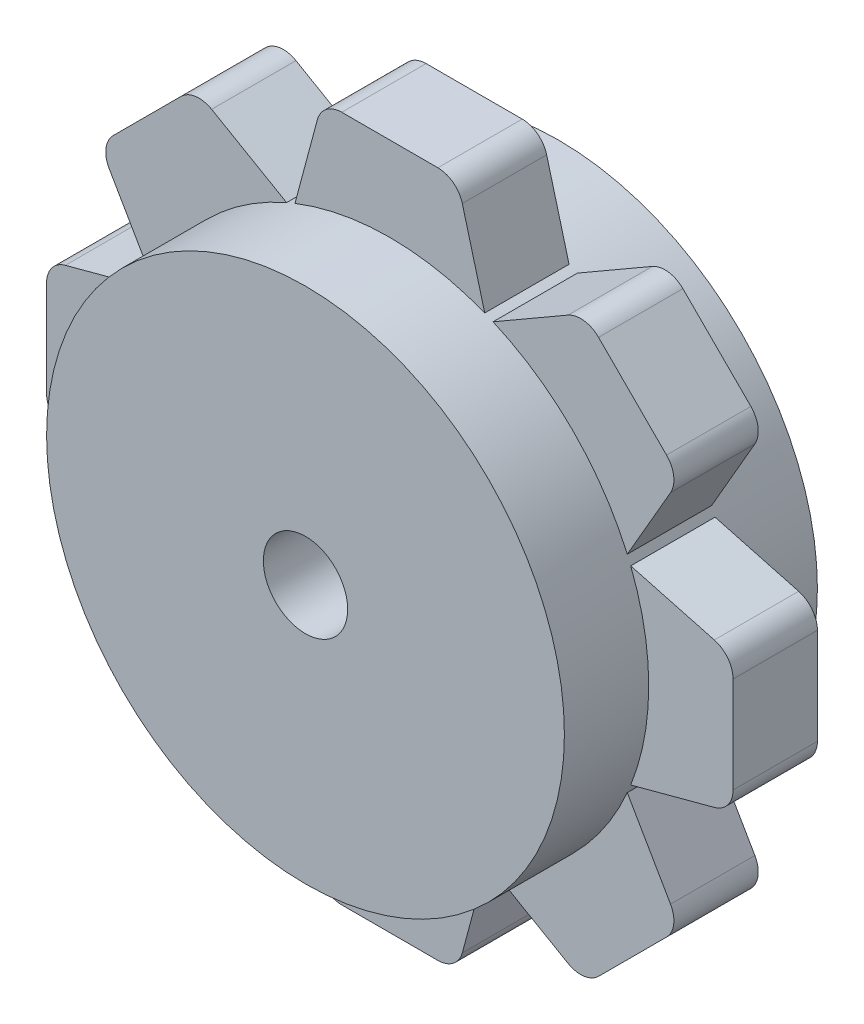
SolidWorks part; units mm, degrees
ref_plane "前视基准面" through (0, 0, 0) normal (0, 0, 1) x (1, 0, 0)
ref_plane "上视基准面" through (0, 0, 0) normal (0, 1, 0) x (1, 0, 0)
ref_plane "右视基准面" through (0, 0, 0) normal (1, 0, 0) x (0, 0, -1)
sketch "草图1" plane through (0, 0, 0) normal (0, 0, 1) x (1, 0, 0)
  line L0 (-5.626, 14.2818) -> (-4, 20.35)
  line L1 (-4, 20.35) -> (4, 20.35)
  line L2 (4, 20.35) -> (5.626, 14.2818)
  line L3 (0, 0) -> (0, 20.35) construction
  line L4 (17.2181, 11.5612) -> (14.0769, 6.1206)
  line L5 (11.5612, 17.2181) -> (17.2181, 11.5612)
  line L6 (6.1206, 14.0769) -> (11.5612, 17.2181)
  line L7 (20.35, -4) -> (14.2818, -5.626)
  line L8 (20.35, 4) -> (20.35, -4)
  line L9 (14.2818, 5.626) -> (20.35, 4)
  line L10 (11.5612, -17.2181) -> (6.1206, -14.0769)
  line L11 (17.2181, -11.5612) -> (11.5612, -17.2181)
  line L12 (14.0769, -6.1206) -> (17.2181, -11.5612)
  line L13 (-4, -20.35) -> (-5.626, -14.2818)
  line L14 (4, -20.35) -> (-4, -20.35)
  line L15 (5.626, -14.2818) -> (4, -20.35)
  line L16 (-17.2181, -11.5612) -> (-14.0769, -6.1206)
  line L17 (-11.5612, -17.2181) -> (-17.2181, -11.5612)
  line L18 (-6.1206, -14.0769) -> (-11.5612, -17.2181)
  line L19 (-20.35, 4) -> (-14.2818, 5.626)
  line L20 (-20.35, -4) -> (-20.35, 4)
  line L21 (-14.2818, -5.626) -> (-20.35, -4)
  line L22 (-11.5612, 17.2181) -> (-6.1206, 14.0769)
  line L23 (-17.2181, 11.5612) -> (-11.5612, 17.2181)
  line L24 (-14.0769, 6.1206) -> (-17.2181, 11.5612)
  circle A0 centre (0, 0) radius 15.35
  circle A1 centre (0, 0) radius 2.5
  point P38 (0, 0)
  dimension "D1" = 30.7
  dimension "D7" = 5
  dimension "D2" = 5
  dimension "D3" = 8
  dimension "D4" = 105
  dimension "D5" = 105
  dimension "D6" = 8
extrude "凸台-拉伸1" add sketch "草图1" along normal blind 15 contours A0 | A1
extrude "凸台-拉伸2" add sketch "草图1<3>" along normal blind 5 from offset 5 contours L3 A0 L2 L1 | A0 L3 L1 L0 | A0 L4 L5 L6 | A0 L7 L8 L9 | A0 L10 L11 L12 | A0 L13 L14 L15 | A0 L16 L17 L18 | A0 L19 L20 L21 | A0 L22 L23 L24 region at (-2.479, 17.5354, 0) region at (-12.3994, 12.3994, 0) region at (2.479, 17.5354, 0) region at (-17.5354, 0, 0) region at (12.3994, 12.3994, 0) region at (-12.3994, -12.3994, 0) region at (17.5354, 0, 0) region at (0, -17.5354, 0) region at (12.3994, -12.3994, 0)
sketch "草图1<3>" plane through (0, 0, 0) normal (0, 0, 1) x (1, 0, 0) same geometry as "草图1"
fillet "圆角1" radius 1.5 16 edges at (-11.5612, 17.2181, 7.5) (-17.2181, 11.5612, 7.5) (-20.35, 4, 7.5) (-20.35, -4, 7.5) (-17.2181, -11.5612, 7.5) (-11.5612, -17.2181, 7.5) (-4, -20.35, 7.5) (4, -20.35, 7.5) (11.5612, -17.2181, 7.5) (17.2181, -11.5612, 7.5) (20.35, -4, 7.5) (20.35, 4, 7.5) (17.2181, 11.5612, 7.5) (11.5612, 17.2181, 7.5) (4, 20.35, 7.5) (-4, 20.35, 7.5)
